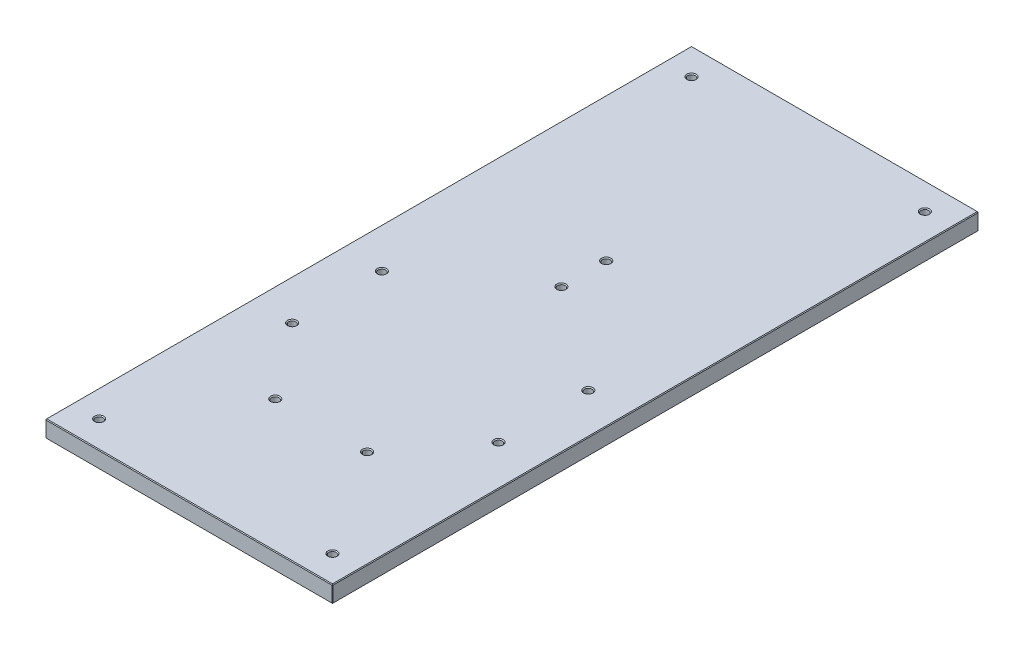
SolidWorks part; units mm, degrees
note: '?' marks a value the reader was unsure of.
material "Pine"
ref_plane "Front Plane" through (0, 0, 0) normal (0, 0, 1) x (1, 0, 0)
ref_plane "Top Plane" through (0, 0, 0) normal (0, 1, 0) x (1, 0, 0)
ref_plane "Right Plane" through (0, 0, 0) normal (1, 0, 0) x (0, 0, -1)
ref_axis "X Axis" through (111.76, 0, 0) along (-1, 0, 0)?
ref_axis "Y Axis" through (0, 3.4925, 0) along (0, -1, 0)?
ref_axis "Z Axis" through (0, 0, -167.64) along (0, 0, 1)?
sketch "Sketch1" plane through (0, 0, 0) normal (0, 1, 0) x (1, 0, 0)
  line L1 (-101.6, -228.6) -> (101.6, -228.6)
  line L2 (-101.6, -228.6) -> (-101.6, 228.6)
  line L3 (-101.6, 228.6) -> (101.6, 228.6)
  line L4 (101.6, -228.6) -> (101.6, 228.6)
  line L5 (0, 228.6) -> (0, -228.6) construction
  line L6 (-101.6, 0) -> (101.6, 0) construction
  point P0 (0, 0)
  dimension "D1" = 457.2
  dimension "D2" = 203.2
extrude "Boss-Extrude1" add sketch "Sketch1" along normal mid plane 12
sketch "Sketch2" plane through (0, 0, 0) normal (0, 1, 0) x (1, 0, 0)
  line L14 (-82.55, -209.55) -> (82.55, -209.55)
  line L15 (82.55, -209.55) -> (82.55, 209.55)
  line L16 (-82.55, 209.55) -> (-82.55, -209.55)
  line L17 (82.55, 209.55) -> (-82.55, 209.55)
  line L18 (-82.55, -209.55) -> (82.55, -209.55) construction
  line L19 (82.55, -209.55) -> (82.55, 209.55) construction
  line L20 (-82.55, 209.55) -> (-82.55, -209.55) construction
  line L21 (82.55, 209.55) -> (-82.55, 209.55) construction
  dimension "D1" = 19.05
sketch "Sketch6" plane through (0, 6, 0) normal (0, 1, 0) x (1, 0, 0)
  point P0 (-82.55, 209.55)
  point P3 (82.55, 209.55)
  point P6 (82.55, -209.55)
  point P9 (-82.55, -209.55)
hole_wizard "#4 (0.209) Diameter Hole1" positions "Sketch6" profile "Sketch4" hole size "#4" standard "ANSI Inch" end condition through all
sketch "Sketch4" plane through (-82.55, 6, -209.55) normal (1, 0, 0) x (0, 0, 1)
  line L0 (0, 0) -> (0, 12)
  line L1 (0, 12) -> (3.2893, 12)
  line L2 (2.6543, 11.365) -> (2.6543, 0.635)
  line L3 (2.6543, 0.635) -> (3.2893, 0)
  line L5 (3.2893, 0) -> (0, 0)
  line L6 (-2.6543, 0.635) -> (-3.2893, 0) construction
  line L7 (3.2893, 12) -> (2.6543, 11.365)
  line L8 (-3.2893, 12) -> (-2.6543, 11.365) construction
  line L11 (0, -6.35) -> (0, 107.95) construction
  dimension "Thru Hole Dia." = 5.3086
  dimension "Thru Hole Depth" = 12
  dimension "Near C'Sink Dia." = 6.5786
  dimension "Near C'Sink Angle" = 90
  dimension "Far C'Sink Dia." = 6.5786
  dimension "Far C'Sink Angle" = 90
chamfer "Chamfer1" distance 0.508 angle 45 12 edges at (101.6, 6, 0) (101.6, -6, 0) (101.6, 0, -228.6) (0, 6, -228.6) (0, -6, -228.6) (-101.6, 0, -228.6) (-101.6, 6, 0) (-101.6, -6, 0) (-101.6, 0, 228.6) (0, 6, 228.6) (101.6, 0, 228.6) (0, -6, 228.6)
sketch "Sketch9" [suppressed] plane through (0, 6, 0) normal (0, 1, 0) x (1, 0, 0)
  point P0 (-32.5, 109.6)
  point P3 (32.5, 109.6)
  point P6 (47.06, 69.85)
  point P9 (-16.44, 69.85)
  point P12 (-16.44, 6.35)
  point P15 (47.06, 6.35)
  point P18 (-44.45, -31.75)
  point P21 (19.05, -31.75)
  point P24 (-44.45, -95.25)
  point P27 (19.05, -95.25)
hole_wizard "#4 (0.209) Diameter Hole2" [suppressed] positions "Sketch9" profile "Sketch8" hole size "#4" standard "ANSI Inch"
sketch "Sketch8" plane through (-32.5, 6, -109.6) normal (1, 0, 0) x (0, 0, 1)
  line L0 (0, 0) -> (0, 12)
  line L1 (0, 12) -> (3.2893, 12)
  line L2 (2.6543, 11.365) -> (2.6543, 0.635)
  line L3 (2.6543, 0.635) -> (3.2893, 0)
  line L5 (3.2893, 0) -> (0, 0)
  line L6 (-2.6543, 0.635) -> (-3.2893, 0) construction
  line L7 (3.2893, 12) -> (2.6543, 11.365)
  line L8 (-3.2893, 12) -> (-2.6543, 11.365) construction
  line L11 (0, -6.35) -> (0, 107.95) construction
  dimension "Thru Hole Dia." = 5.3086
  dimension "Thru Hole Depth" = 12
  dimension "Near C'Sink Dia." = 6.5786
  dimension "Near C'Sink Angle" = 90
  dimension "Far C'Sink Dia." = 6.5786
  dimension "Far C'Sink Angle" = 90
sketch "Sketch12" plane through (0, 6, 0) normal (0, 1, 0) x (1, 0, 0)
  point P0 (-32.5, -135)
  point P3 (32.5, -135)
  point P6 (0, 34.925)
  point P9 (0, 66.675)
  point P12 (-73.025, -19.05)
  point P15 (-73.025, -82.55)
  point P18 (73.025, -82.55)
  point P21 (73.025, -19.05)
hole_wizard "#4 (0.209) Diameter Hole3" positions "Sketch12" profile "Sketch11" hole size "#4" standard "ANSI Inch" end condition through all
sketch "Sketch11" plane through (-32.5, 6, 135) normal (1, 0, 0) x (0, 0, 1)
  line L0 (0, 0) -> (0, 12)
  line L1 (0, 12) -> (3.2893, 12)
  line L2 (2.6543, 11.365) -> (2.6543, 0.635)
  line L3 (2.6543, 0.635) -> (3.2893, 0)
  line L5 (3.2893, 0) -> (0, 0)
  line L6 (-2.6543, 0.635) -> (-3.2893, 0) construction
  line L7 (3.2893, 12) -> (2.6543, 11.365)
  line L8 (-3.2893, 12) -> (-2.6543, 11.365) construction
  line L11 (0, -6.35) -> (0, 107.95) construction
  dimension "Thru Hole Dia." = 5.3086
  dimension "Thru Hole Depth" = 12
  dimension "Near C'Sink Dia." = 6.5786
  dimension "Near C'Sink Angle" = 90
  dimension "Far C'Sink Dia." = 6.5786
  dimension "Far C'Sink Angle" = 90
move or copy body "Body-Move/Copy1" [suppressed] bodies to move or copy 102 parameters "D1"=0, "D2"=0, "D3"=0
move or copy body "Body-Move/Copy2" [suppressed] bodies to move or copy 103 parameters "D1"=0, "D2"=0, "D3"=0
